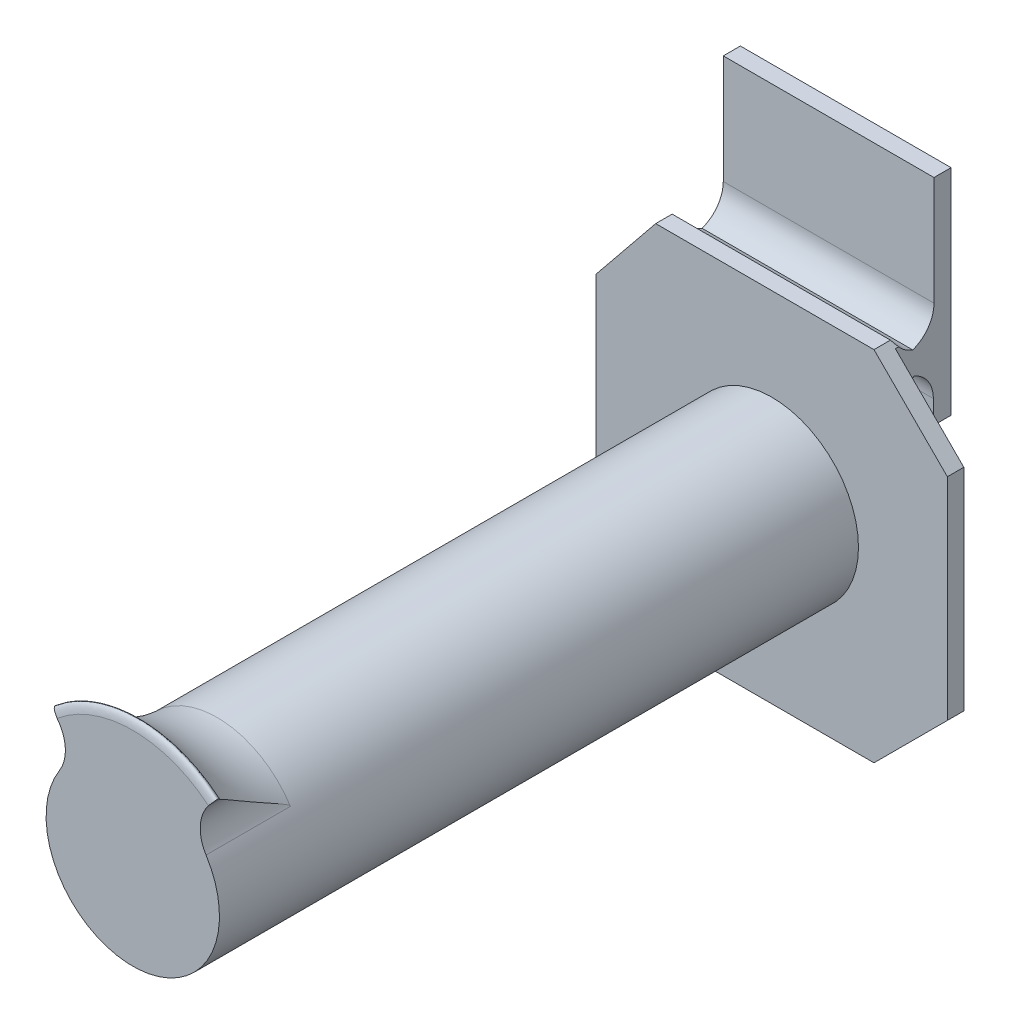
SolidWorks part; units mm, degrees
ref_plane "Front Plane" through (0, 0, 0) normal (0, 0, 1) x (1, 0, 0)
ref_plane "Top Plane" through (0, 0, 0) normal (0, 1, 0) x (1, 0, 0)
ref_plane "Right Plane" through (0, 0, 0) normal (1, 0, 0) x (0, 0, -1)
sketch "Sketch1" plane through (0, 0, 0) normal (0, 0, 1) x (1, 0, 0)
  circle A0 centre (0, 0) radius 13.7
extrude "Boss-Extrude1" add sketch "Sketch1" along normal blind 101
sketch "Sketch5" plane through (0, 0, 0) normal (0, 0, -1) x (-1, 0, 0)
  line L1 (27.75, 28.2807) -> (-27.75, 28.2807)
  line L2 (27.75, 28.2807) -> (27.75, -28.2807)
  line L3 (27.75, -28.2807) -> (-27.75, -28.2807)
  line L4 (-27.75, 28.2807) -> (-27.75, -28.2807)
  line L5 (27.75, 28.2807) -> (-27.75, -28.2807) construction
  line L6 (27.75, -28.2807) -> (-27.75, 28.2807) construction
  point P0 (0, 0)
extrude "Boss-Extrude2" add sketch "Sketch5" along normal blind 2.6 contours L1 L4 L3 L2
sketch "Sketch6" plane through (0, 0, -2.6) normal (0, 0, -1) x (-1, 0, 0)
  line L0 (-27.75, 16.6807) -> (-27.75, 28.2807)
  line L2 (27.75, 28.2807) -> (-27.75, 28.2807) construction
  line L3 (-16.15, 28.2807) -> (18.35, 28.2807) construction
  line L4 (-27.75, 0) -> (27.75, 0) construction
  line L5 (-27.75, 28.2807) -> (-27.75, -28.2807) construction
  line L6 (27.75, 28.2807) -> (27.75, -28.2807) construction
  line L7 (-16.15, -28.2807) -> (18.35, -28.2807)
  line L8 (-16.15, -28.2807) -> (-27.75, -16.6807)
  line L9 (-16.15, 28.2807) -> (-27.75, 16.6807)
  line L10 (1.1, -28.2807) -> (1.1, 28.2807) construction
  line L11 (18.35, -28.2807) -> (27.75, -18.8807)
  line L12 (27.75, -18.8807) -> (27.75, 16.6807)
  line L13 (27.75, 16.6807) -> (18.35, 28.2807)
  line L14 (-27.75, 16.6807) -> (-27.75, -16.6807) construction
  line L15 (-27.75, 28.2807) -> (-16.15, 28.2807)
  line L17 (18.35, 28.2807) -> (27.75, 28.2807)
  line L18 (27.75, 28.2807) -> (27.75, 16.6807)
  line L19 (27.75, -28.2807) -> (27.75, -18.8807)
  line L20 (18.35, -28.2807) -> (27.75, -28.2807)
  line L21 (-16.15, -28.2807) -> (-27.75, -28.2807)
  line L22 (-27.75, -28.2807) -> (-27.75, -16.6807)
  line M1 (27.75, -28.2807) -> (27.75, 28.2807)
  line M2 (27.75, 28.2807) -> (-27.75, 28.2807)
  line M3 (-27.75, 28.2807) -> (-27.75, -28.2807)
  line M4 (-27.75, -28.2807) -> (27.75, -28.2807)
extrude "Cut-Extrude4" cut sketch "Sketch6" against normal blind 2.6 contours L13 M1 M2 | L8 M4 M3 | L11 M4 M1 | L0 L15 L9 region at (23.8833, -24.414, -2.6) region at (-24.6167, 24.414, -2.6) region at (-24.6167, -25.1473, -2.6)
sketch "Sketch7" plane through (0, 0, -2.6) normal (0, 0, -1) x (-1, 0, 0)
  line L0 (1.1, 28.2807) -> (1.1, 25.6807) construction
  line L1 (18.35, 28.2807) -> (-16.15, 28.2807) construction
  line L2 (1.1, 25.6807) -> (16.3666, 25.6807)
  line L3 (16.3666, 25.6807) -> (16.3666, 22.6807)
  line L4 (-16.9334, 22.6807) -> (-16.9334, 25.6807)
  line L5 (16.3666, 22.6807) -> (-16.9334, 22.6807)
  line L6 (-16.9334, 25.6807) -> (1.1, 25.6807)
extrude "Boss-Extrude4" add sketch "Sketch7" along normal blind 6 contours L5 L4 L6 L2 L3
sketch "Sketch8" plane through (0, 0, -8.6) normal (0, 0, -1) x (-1, 0, 0)
  line L1 (-16.9334, 25.6807) -> (16.3666, 25.6807)
  line L2 (-16.9334, 25.6807) -> (-16.9334, 13.9807)
  line L3 (-16.9334, 13.9807) -> (16.3666, 13.9807)
  line L4 (16.3666, 25.6807) -> (16.3666, 13.9807)
  dimension "D1" = 11.7
extrude "Boss-Extrude5" add sketch "Sketch8" along normal blind 2.8
sketch "Sketch9" plane through (0, 25.6807, 0) normal (0, 1, 0) x (1, 0, 0)
  line L0 (16.9334, 11.4) -> (16.9334, 2.6) construction
  line L1 (-16.3666, 11.4) -> (16.9334, 11.4)
  line L2 (-16.3666, 11.4) -> (-16.3666, 8.7)
  line L3 (-16.3666, 8.7) -> (16.9334, 8.7)
  line L4 (16.9334, 11.4) -> (16.9334, 8.7)
  dimension "D1" = 2.7
extrude "Boss-Extrude6" add sketch "Sketch9" along normal blind 22.2
fillet "Fillet2" radius 5 4 edges at (0.2834, 25.6807, -2.6) (0.2834, 22.6807, -2.6) (0.2834, 25.6807, -8.7)
sketch3d "3DSketch3"
  circle A0 centre (0, 0, 101) radius 13.7 construction
  point P2 (0, 0, 114.7)
sketch "Sketch10" plane through (0, 0, 0) normal (-1, 0, 0) x (0, 0, 1)
  line L0 (101, -13.7) -> (101, 13.7) construction
  line L1 (101, -13.7) -> (101, 13.7) construction
  line L2 (101, 13.7) -> (101, 18.6075)
  line L3 (101, 13.7) -> (87.6723, 13.7)
  arc A0 (99.2892, 18.6075) -> (87.6723, 13.7) centre (87.0391, 31.4021) cw
  spline S0 degree 2 poles (101, 18.6075) (100.7188, 21.2824) (99.2892, 18.6075) knots 0 0 0 1 1 1
sketch "Sketch11" plane through (0, 0, 0) normal (-1, 0, 0) x (0, 0, 1)
  line L0 (101.1008, 0) -> (0, 0) construction
revolve "Revolve1" add sketch "Sketch10" angle 40 about L0 other way angle 40
fillet "Fillet4" radius 6 1 edges at (8.8062, 10.4948, 94.3362)
fillet "Fillet5" radius 6 1 edges at (-8.8062, 10.4948, 94.3362)
